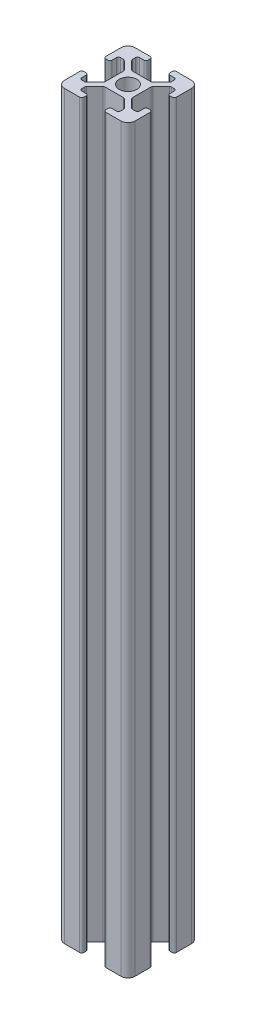
SolidWorks part; units mm, degrees
ref_plane "前视基准面" through (0, 0, 0) normal (0, 0, 1) x (1, 0, 0)
ref_plane "上视基准面" through (0, 0, 0) normal (0, 1, 0) x (1, 0, 0)
ref_plane "右视基准面" through (0, 0, 0) normal (1, 0, 0) x (0, 0, -1)
sketch "草图1" plane through (0, 0, 0) normal (0, 1, 0) x (1, 0, 0)
  line L0 (3.1, 8.8) -> (3.1, 9.4)
  line L1 (-10, -10) -> (10, -10) construction
  line L2 (-10, -10) -> (-10, 10) construction
  line L3 (-10, 10) -> (10, 10) construction
  line L4 (10, -10) -> (10, 10) construction
  line L5 (-10, -10) -> (10, 10) construction
  line L6 (-10, 10) -> (10, -10) construction
  line L7 (3.7, 10) -> (8, 10)
  line L8 (0, 10) -> (0, -10) construction
  line L9 (3.7, 8.2) -> (4.9, 8.2)
  line L10 (5.3243, 6.3849) -> (3.0151, 4.0757)
  line L11 (2.5908, 3.9) -> (0, 3.9)
  line L12 (5.5, 7.6) -> (5.5, 6.8092)
  line L13 (10, 3.7) -> (10, 8)
  line L14 (8.8, 3.1) -> (9.4, 3.1)
  line L15 (8.2, 3.7) -> (8.2, 4.9)
  line L16 (7.6, 5.5) -> (6.8092, 5.5)
  line L17 (6.3849, 5.3243) -> (4.0757, 3.0151)
  line L18 (3.9, 2.5908) -> (3.9, 0)
  line L19 (3.9, -2.5908) -> (3.9, 0)
  line L20 (2.5908, -3.9) -> (0, -3.9)
  line L21 (5.3243, -6.3849) -> (3.0151, -4.0757)
  line L22 (6.3849, -5.3243) -> (4.0757, -3.0151)
  line L23 (5.5, -7.6) -> (5.5, -6.8092)
  line L24 (3.7, -8.2) -> (4.9, -8.2)
  line L25 (3.1, -8.8) -> (3.1, -9.4)
  line L26 (3.7, -10) -> (8, -10)
  line L27 (10, -3.7) -> (10, -8)
  line L28 (8.8, -3.1) -> (9.4, -3.1)
  line L29 (8.2, -3.7) -> (8.2, -4.9)
  line L30 (7.6, -5.5) -> (6.8092, -5.5)
  line L31 (-2.5908, -3.9) -> (0, -3.9)
  line L32 (-3.9, -2.5908) -> (-3.9, 0)
  line L33 (-6.3849, -5.3243) -> (-4.0757, -3.0151)
  line L34 (-5.3243, -6.3849) -> (-3.0151, -4.0757)
  line L35 (-7.6, -5.5) -> (-6.8092, -5.5)
  line L36 (-8.2, -3.7) -> (-8.2, -4.9)
  line L37 (-8.8, -3.1) -> (-9.4, -3.1)
  line L38 (-10, -3.7) -> (-10, -8)
  line L39 (-3.7, -10) -> (-8, -10)
  line L40 (-3.1, -8.8) -> (-3.1, -9.4)
  line L41 (-3.7, -8.2) -> (-4.9, -8.2)
  line L42 (-5.5, -7.6) -> (-5.5, -6.8092)
  line L43 (-3.9, 2.5908) -> (-3.9, 0)
  line L44 (-2.5908, 3.9) -> (0, 3.9)
  line L45 (-5.3243, 6.3849) -> (-3.0151, 4.0757)
  line L46 (-6.3849, 5.3243) -> (-4.0757, 3.0151)
  line L47 (-5.5, 7.6) -> (-5.5, 6.8092)
  line L48 (-3.7, 8.2) -> (-4.9, 8.2)
  line L49 (-3.1, 8.8) -> (-3.1, 9.4)
  line L50 (-3.7, 10) -> (-8, 10)
  line L51 (-10, 3.7) -> (-10, 8)
  line L52 (-8.8, 3.1) -> (-9.4, 3.1)
  line L53 (-8.2, 3.7) -> (-8.2, 4.9)
  line L54 (-7.6, 5.5) -> (-6.8092, 5.5)
  circle A0 centre (0, 0) radius 2.5
  arc A1 (3.0151, 4.0757) -> (2.5908, 3.9) centre (2.5908, 4.5) cw
  arc A2 (5.5, 6.8092) -> (5.3243, 6.3849) centre (4.9, 6.8092) cw
  arc A3 (5.5, 7.6) -> (4.9, 8.2) centre (4.9, 7.6) ccw
  arc A4 (3.1, 8.8) -> (3.7, 8.2) centre (3.7, 8.8) ccw
  arc A5 (3.7, 10) -> (3.1, 9.4) centre (3.7, 9.4) ccw
  arc A6 (10, 3.7) -> (9.4, 3.1) centre (9.4, 3.7) cw
  arc A7 (8.8, 3.1) -> (8.2, 3.7) centre (8.8, 3.7) cw
  arc A8 (7.6, 5.5) -> (8.2, 4.9) centre (7.6, 4.9) cw
  arc A9 (6.8092, 5.5) -> (6.3849, 5.3243) centre (6.8092, 4.9) ccw
  arc A10 (4.0757, 3.0151) -> (3.9, 2.5908) centre (4.5, 2.5908) ccw
  arc A11 (10, 8) -> (8, 10) centre (8, 8) ccw
  arc A12 (3.0151, -4.0757) -> (2.5908, -3.9) centre (2.5908, -4.5) ccw
  arc A13 (4.0757, -3.0151) -> (3.9, -2.5908) centre (4.5, -2.5908) cw
  arc A14 (5.5, -6.8092) -> (5.3243, -6.3849) centre (4.9, -6.8092) ccw
  arc A15 (6.8092, -5.5) -> (6.3849, -5.3243) centre (6.8092, -4.9) cw
  arc A16 (5.5, -7.6) -> (4.9, -8.2) centre (4.9, -7.6) cw
  arc A17 (3.1, -8.8) -> (3.7, -8.2) centre (3.7, -8.8) cw
  arc A18 (3.7, -10) -> (3.1, -9.4) centre (3.7, -9.4) cw
  arc A19 (8, -10) -> (10, -8) centre (8, -8) ccw
  arc A20 (10, -3.7) -> (9.4, -3.1) centre (9.4, -3.7) ccw
  arc A21 (8.8, -3.1) -> (8.2, -3.7) centre (8.8, -3.7) ccw
  arc A22 (7.6, -5.5) -> (8.2, -4.9) centre (7.6, -4.9) ccw
  arc A23 (-4.0757, -3.0151) -> (-3.9, -2.5908) centre (-4.5, -2.5908) ccw
  arc A24 (-3.0151, -4.0757) -> (-2.5908, -3.9) centre (-2.5908, -4.5) cw
  arc A25 (-6.8092, -5.5) -> (-6.3849, -5.3243) centre (-6.8092, -4.9) ccw
  arc A26 (-5.5, -6.8092) -> (-5.3243, -6.3849) centre (-4.9, -6.8092) cw
  arc A27 (-7.6, -5.5) -> (-8.2, -4.9) centre (-7.6, -4.9) cw
  arc A28 (-8.8, -3.1) -> (-8.2, -3.7) centre (-8.8, -3.7) cw
  arc A29 (-10, -3.7) -> (-9.4, -3.1) centre (-9.4, -3.7) cw
  arc A30 (-10, -8) -> (-8, -10) centre (-8, -8) ccw
  arc A31 (-3.7, -10) -> (-3.1, -9.4) centre (-3.7, -9.4) ccw
  arc A32 (-3.1, -8.8) -> (-3.7, -8.2) centre (-3.7, -8.8) ccw
  arc A33 (-5.5, -7.6) -> (-4.9, -8.2) centre (-4.9, -7.6) ccw
  arc A34 (-3.0151, 4.0757) -> (-2.5908, 3.9) centre (-2.5908, 4.5) ccw
  arc A35 (-4.0757, 3.0151) -> (-3.9, 2.5908) centre (-4.5, 2.5908) cw
  arc A36 (-5.5, 6.8092) -> (-5.3243, 6.3849) centre (-4.9, 6.8092) ccw
  arc A37 (-6.8092, 5.5) -> (-6.3849, 5.3243) centre (-6.8092, 4.9) cw
  arc A38 (-5.5, 7.6) -> (-4.9, 8.2) centre (-4.9, 7.6) cw
  arc A39 (-3.1, 8.8) -> (-3.7, 8.2) centre (-3.7, 8.8) cw
  arc A40 (-3.7, 10) -> (-3.1, 9.4) centre (-3.7, 9.4) cw
  arc A41 (-8, 10) -> (-10, 8) centre (-8, 8) ccw
  arc A42 (-10, 3.7) -> (-9.4, 3.1) centre (-9.4, 3.7) ccw
  arc A43 (-8.8, 3.1) -> (-8.2, 3.7) centre (-8.8, 3.7) ccw
  arc A44 (-7.6, 5.5) -> (-8.2, 4.9) centre (-7.6, 4.9) ccw
  point P0 (0, 0)
  point P20 (5.5, 6.5607)
  point P25 (3.1, 8.2)
  point P28 (3.1, 10)
  point P156 (0, 0)
  dimension "D3" = 5
  dimension "D9" = 0.6
  dimension "D10" = 2
  dimension "D1" = 20
  dimension "D2" = 20
  dimension "D4" = 6.1
  dimension "D5" = 1.5
  dimension "D6" = 1.8
  dimension "D7" = 3.1
  dimension "D8" = 4.5
  dimension "D11" = 4
extrude "凸台-拉伸1" add sketch "草图1" along normal blind 210
